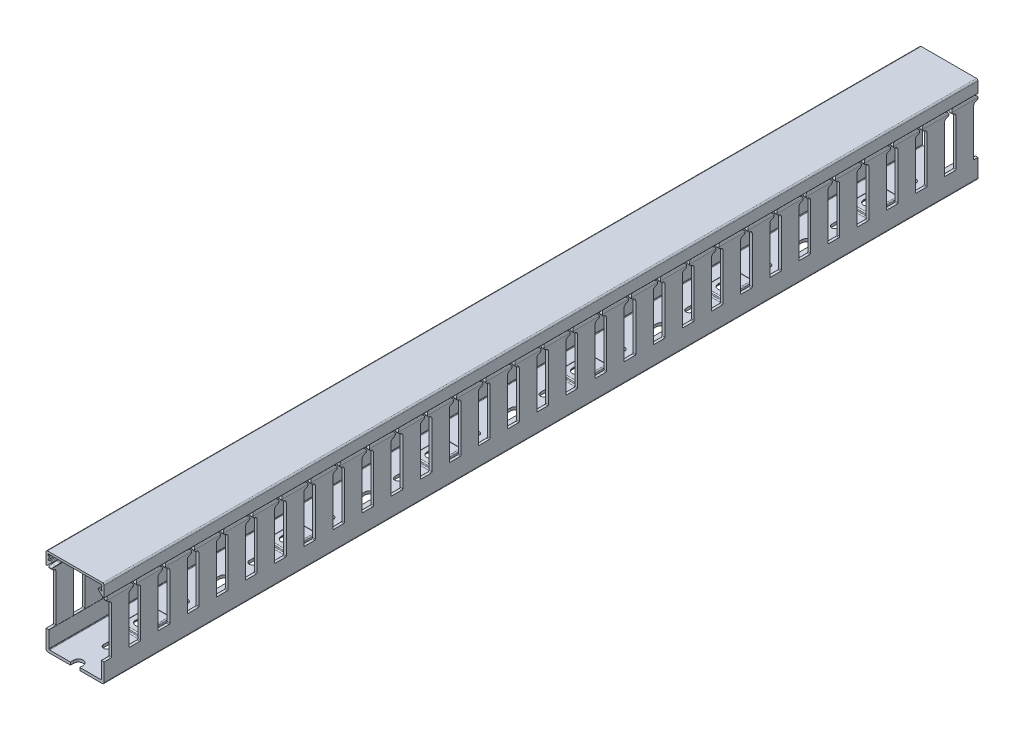
SolidWorks part; units mm, degrees
ref_plane "Front Plane" through (0, 0, 0) normal (0, 0, 1) x (1, 0, 0)
ref_plane "Top Plane" through (0, 0, 0) normal (0, 1, 0) x (1, 0, 0)
ref_plane "Right Plane" through (0, 0, 0) normal (1, 0, 0) x (0, 0, -1)
sketch "Sketch1" plane through (0, 0, 0) normal (0, 0, 1) x (1, 0, 0)
  line L0 (-18.2, -27.85) -> (-17.973, -27.983)
  line L1 (-20, -28.55) -> (-20, 19.1871)
  line L2 (-20, 21.7598) -> (-20, 29.05)
  line L3 (-18.5, 28.35) -> (-18.5, 27.55)
  line L4 (-18.5, 25.25) -> (-18.5, 25.058)
  line L5 (-19.6147, 20.1908) -> (-15.6798, 24.5609)
  line L6 (-17.8221, 24.7703) -> (-17.3671, 25.2097)
  line L7 (-15.9527, 24.4903) -> (-19.1527, 21.4001)
  line L8 (-18.1, 18.8416) -> (-18.1, -16.3923)
  line L9 (-18.1, -16.5077) -> (-18.1, -27.65)
  line L10 (-18, 25.55) -> (-18, 27.25)
  line L11 (-14.8603, 22.6316) -> (-17.9716, 19.1762)
  line L12 (-18.2, -16.45) -> (-18.1, -16.5077)
  line L13 (-13.3, 25.85) -> (-13.3, 24.6071)
  line L14 (-7, -28.15) -> (-7, -25.65)
  line L15 (-18.5, -30.05) -> (18.5, -30.05)
  line L16 (0, -30.05) -> (0, 30.05) construction
  line L18 (-17.6, -28.15) -> (17.6, -28.15)
  line L19 (-17.973, -27.983) -> (-17.973, -27.7208) construction
  line L20 (-18.082, -27.7829) -> (-17.973, -27.7208) construction
  line L21 (18.1, -16.5077) -> (18.1, -16.3923) construction
  line L23 (-7, -25.65) -> (7, -25.65)
  line L24 (-18.1, -16.5077) -> (-18.1, -16.3923) construction
  line L25 (-2.25, -30.05) -> (-2.25, -28.15)
  line L26 (2.25, -30.05) -> (2.25, -28.15)
  line L27 (7, -28.15) -> (7, -25.65)
  line L28 (17.973, -27.717) -> (18.082, -27.7829) construction
  line L29 (-18.1, -16.3923) -> (-18.2, -16.45)
  line L30 (18.1, -16.3923) -> (18.2, -16.45)
  line L31 (-18.082, -27.7829) -> (-18.2, -27.85)
  line L33 (18.4, 25.35) -> (18.2, 25.35)
  line L34 (-16.3, 25.35) -> (-17.0198, 25.35)
  line L35 (-18.4, 25.35) -> (-18.2, 25.35)
  line L36 (16.3, 25.35) -> (17.0198, 25.35)
  line L38 (-18.2, 27.45) -> (-18.4, 27.45)
  line L39 (18.2, 27.45) -> (18.4, 27.45)
  line L40 (16.0883, 27.65) -> (15.1, 27.65)
  line L41 (-16.0883, 27.65) -> (-15.1, 27.65)
  line L42 (-18.3, 28.55) -> (18.3, 28.55)
  line L44 (19, 30.05) -> (-19, 30.05)
  line L46 (-16.3812, 25.7055) -> (-17.6188, 25.3739)
  line L47 (16.3812, 25.7055) -> (17.6188, 25.3739)
  line L48 (13.3, 25.85) -> (13.3, 24.6071)
  line L49 (18, 25.55) -> (18, 27.25)
  line L50 (18.1, 18.8416) -> (18.1, -16.3923)
  line L51 (18.1, -16.5077) -> (18.1, -27.65)
  line L52 (18.5, 28.35) -> (18.5, 27.55)
  line L53 (18.5, 25.25) -> (18.5, 25.058)
  line L54 (18.2, -16.45) -> (18.1, -16.5077)
  line L55 (14.8603, 22.6316) -> (17.9716, 19.1762)
  line L56 (20, -28.55) -> (20, 19.1871)
  line L57 (20, 21.7598) -> (20, 29.05)
  line L58 (15.9527, 24.4903) -> (19.1527, 21.4001)
  line L59 (17.8221, 24.7703) -> (17.3671, 25.2097)
  line L60 (19.6147, 20.1908) -> (15.6798, 24.5609)
  line L61 (18.2, -27.85) -> (17.973, -27.983)
  line L62 (-2.25, -29.1) -> (2.25, -29.1) construction
  line L63 (-7, -26.9) -> (7, -26.9) construction
  line L64 (0, -29.1) -> (0, -26.9) construction
  line L68 (17.973, -27.983) -> (17.973, -27.717) construction
  line L69 (20, -4.6815) -> (18.1, -4.6815) construction
  line L70 (-20, -4.6815) -> (-18.1, -4.6815) construction
  line L71 (18.082, -27.7829) -> (18.2, -27.85)
  line L72 (16.4159, 20.9039) -> (17.8279, 22.1752) construction
  line L73 (18.2, -27.85) -> (17.973, -27.85) construction
  line L74 (20, 19.1871) -> (20, 19.7629) construction
  line L75 (20, 19.7629) -> (19.6147, 20.1908) construction
  line L76 (18.1, 18.8416) -> (18.1, 19.0335) construction
  line L77 (18.1, 19.0335) -> (17.9716, 19.1762) construction
  line L78 (20, 21.7598) -> (20, 20.5819) construction
  line L79 (20, 20.5819) -> (19.1527, 21.4001) construction
  line L80 (18.3, 28.55) -> (18.3, 30.05) construction
  line L81 (18.5, 28.35) -> (20, 28.35) construction
  line L82 (17.5946, 24.99) -> (16.5526, 23.911) construction
  line L83 (14.0985, 26.3171) -> (16.3812, 25.7055) construction
  line L84 (14.0985, 26.3171) -> (15.6798, 24.5609) construction
  line L85 (15.1, 24.6071) -> (15.1, 25.85) construction
  line L86 (15.1, 25.85) -> (16.0883, 25.85) construction
  line L87 (16.0883, 25.85) -> (16.0883, 24.6071) construction
  line L88 (16.0883, 24.6071) -> (15.1, 24.6071) construction
  arc A0 (-20, -28.55) -> (-18.5, -30.05) centre (-18.5, -28.55) ccw
  arc A1 (-18.1, -27.65) -> (-18.082, -27.7829) centre (-17.6, -27.65) ccw
  arc A2 (-17.973, -27.983) -> (-17.6, -28.15) centre (-17.6, -27.65) ccw
  arc A3 (-17.5208, 26.94) -> (-18.1276, 26.6686) centre (-15.7875, 22.25) ccw
  arc A4 (-14.8603, 22.6316) -> (-13.7623, 23.4026) centre (-15.9918, 25.41) ccw
  arc A5 (-16.0883, 27.65) -> (-17.5208, 26.94) centre (-16.0883, 25.85) ccw
  arc A6 (-13.3, 25.85) -> (-15.1, 27.65) centre (-15.1, 25.85) ccw
  arc A7 (-13.7623, 23.4026) -> (-13.3, 24.6071) centre (-15.1, 24.6071) ccw
  arc A8 (-19.6147, 20.1908) -> (-20, 19.1871) centre (-18.5, 19.1871) ccw
  arc A9 (-19, 30.05) -> (-20, 29.05) centre (-19, 29.05) ccw
  arc A10 (-15.6798, 24.5609) -> (-16.3812, 25.7055) centre (-16.2, 25.0293) ccw
  arc A11 (-18.1276, 26.6686) -> (-17.6188, 25.3739) centre (-17.8, 26.05) ccw
  arc A12 (-17.0198, 25.35) -> (-17.3671, 25.2097) centre (-17.0198, 24.85) ccw
  arc A13 (-15.9527, 24.4903) -> (-16.3, 25.35) centre (-16.3, 24.85) ccw
  arc A14 (-20, 21.7598) -> (-19.1527, 21.4001) centre (-19.5, 21.7598) ccw
  arc A15 (-17.9716, 19.1762) -> (-18.1, 18.8416) centre (-17.6, 18.8416) ccw
  arc A16 (-18.5, 25.058) -> (-17.8221, 24.7703) centre (-18.1, 25.058) ccw
  arc A17 (-18.3, 28.55) -> (-18.5, 28.35) centre (-18.3, 28.35) ccw
  arc A18 (-18, 27.25) -> (-18.2, 27.45) centre (-18.2, 27.25) ccw
  arc A19 (-18.2, 25.35) -> (-18, 25.55) centre (-18.2, 25.55) ccw
  arc A20 (-18.4, 25.35) -> (-18.5, 25.25) centre (-18.4, 25.25) ccw
  arc A21 (-18.5, 27.55) -> (-18.4, 27.45) centre (-18.4, 27.55) ccw
  arc A22 (18.5, -30.05) -> (20, -28.55) centre (18.5, -28.55) ccw
  arc A23 (17.6, -28.15) -> (17.973, -27.983) centre (17.6, -27.65) ccw
  arc A24 (18.082, -27.7829) -> (18.1, -27.65) centre (17.6, -27.65) ccw
  arc A25 (18.1276, 26.6686) -> (17.5208, 26.94) centre (15.7875, 22.25) ccw
  arc A26 (13.7623, 23.4026) -> (14.8603, 22.6316) centre (15.9918, 25.41) ccw
  arc A27 (13.3, 24.6071) -> (13.7623, 23.4026) centre (15.1, 24.6071) ccw
  arc A28 (15.1, 27.65) -> (13.3, 25.85) centre (15.1, 25.85) ccw
  arc A29 (17.5208, 26.94) -> (16.0883, 27.65) centre (16.0883, 25.85) ccw
  arc A30 (20, 19.1871) -> (19.6147, 20.1908) centre (18.5, 19.1871) ccw
  arc A31 (20, 29.05) -> (19, 30.05) centre (19, 29.05) ccw
  arc A32 (17.6188, 25.3739) -> (18.1276, 26.6686) centre (17.8, 26.05) ccw
  arc A33 (16.3812, 25.7055) -> (15.6798, 24.5609) centre (16.2, 25.0293) ccw
  arc A34 (17.3671, 25.2097) -> (17.0198, 25.35) centre (17.0198, 24.85) ccw
  arc A35 (16.3, 25.35) -> (15.9527, 24.4903) centre (16.3, 24.85) ccw
  arc A36 (19.1527, 21.4001) -> (20, 21.7598) centre (19.5, 21.7598) ccw
  arc A37 (18.1, 18.8416) -> (17.9716, 19.1762) centre (17.6, 18.8416) ccw
  arc A38 (17.8221, 24.7703) -> (18.5, 25.058) centre (18.1, 25.058) ccw
  arc A39 (18.5, 28.35) -> (18.3, 28.55) centre (18.3, 28.35) ccw
  arc A40 (18.2, 27.45) -> (18, 27.25) centre (18.2, 27.25) ccw
  arc A41 (18, 25.55) -> (18.2, 25.35) centre (18.2, 25.55) ccw
  arc A42 (18.5, 25.25) -> (18.4, 25.35) centre (18.4, 25.25) ccw
  arc A43 (18.4, 27.45) -> (18.5, 27.55) centre (18.4, 27.55) ccw
  point P188 (0, 28.55)
  dimension "D2" = 1.5
  dimension "D9" = 0.5
  dimension "D12" = 1
  dimension "D13" = 1.8
  dimension "D14" = 0.2
  dimension "D15" = 0.1
  dimension "D16" = 0.7
  dimension "D28" = 0.4
  dimension "D29" = 3
  dimension "D30" = 5
  dimension "D1" = 14
  dimension "Height" = 60.1
  dimension "Width" = 40
  dimension "D3" = 1.9
  dimension "D4" = 1.5
  dimension "D5" = 0.1155
  dimension "D6" = 46
  dimension "D7" = 138
  dimension "D10" = 2.5
  dimension "D11" = 4.5
  dimension "D18" = 0.3
  dimension "D19" = 0.266
  dimension "D20" = 60
  dimension "D21" = 8.6165
  dimension "D22" = 9.4681
  dimension "D23" = 0.5
  dimension "D24" = 1.1
  dimension "D25" = 2.1
  dimension "D26" = 0.9
  dimension "D27" = 4.8
  dimension "D31" = 0.9883
  dimension "D32" = 1.2429
  dimension "D33" = 33
  dimension "D34" = 5.0184
  dimension "D35" = 4.2208
  dimension "Slot Height" = 13.6
sketch "Sketch2" plane through (0, 0, 0) normal (0, 1, 0) x (1, 0, 0)
  line L1 (-20, 300) -> (20, 300)
  line L2 (-20, 300) -> (-20, -300)
  line L3 (-20, -300) -> (20, -300)
  line L4 (20, 300) -> (20, -300)
  line L5 (-20, 300) -> (20, -300) construction
  line L6 (-20, -300) -> (20, 300) construction
  line L9 (0, -305.25) -> (0, -297.75) construction
  line L10 (-3.25, -305.25) -> (-3.25, -297.75)
  line L11 (3.25, -305.25) -> (3.25, -297.75)
  line L15 (0, -294.5) -> (0, -297.75) construction
  line L16 (0, -305.25) -> (0, -308.5) construction
  line L17 (0, -278.25) -> (0, -274.75) construction
  line L18 (-2.25, -278.25) -> (-2.25, -274.75)
  line L19 (2.25, -278.25) -> (2.25, -274.75)
  line L23 (0, -278.25) -> (0, -280.5) construction
  line L24 (0, -255.25) -> (0, -247.75) construction
  line L26 (0, -274.75) -> (0, -272.5) construction
  line L30 (7, -262.2071) -> (-7, -262.2071)
  line L31 (7, -262.2071) -> (7, -240.7929)
  line L32 (7, -240.7929) -> (-7, -240.7929)
  line L33 (-7, -262.2071) -> (-7, -240.7929)
  line L34 (-3.25, -255.25) -> (-3.25, -247.75)
  line L35 (3.25, -255.25) -> (3.25, -247.75)
  line L36 (0, -205.25) -> (0, -197.75) construction
  line L37 (-3.25, -205.25) -> (-3.25, -197.75)
  line L38 (3.25, -205.25) -> (3.25, -197.75)
  line L45 (0, -228.25) -> (0, -224.75) construction
  line L46 (-2.25, -228.25) -> (-2.25, -224.75)
  line L47 (2.25, -228.25) -> (2.25, -224.75)
  arc A2 (-3.25, -305.25) -> (3.25, -305.25) centre (0, -305.25) ccw
  arc A3 (3.25, -297.75) -> (-3.25, -297.75) centre (0, -297.75) ccw
  arc A6 (-2.25, -278.25) -> (2.25, -278.25) centre (0, -278.25) ccw
  arc A7 (2.25, -274.75) -> (-2.25, -274.75) centre (0, -274.75) ccw
  arc A10 (-3.25, -255.25) -> (3.25, -255.25) centre (0, -255.25) ccw
  arc A11 (3.25, -247.75) -> (-3.25, -247.75) centre (0, -247.75) ccw
  arc A12 (-3.25, -205.25) -> (3.25, -205.25) centre (0, -205.25) ccw
  arc A13 (3.25, -197.75) -> (-3.25, -197.75) centre (0, -197.75) ccw
  arc A18 (-2.25, -228.25) -> (2.25, -228.25) centre (0, -228.25) ccw
  arc A19 (2.25, -224.75) -> (-2.25, -224.75) centre (0, -224.75) ccw
  point P0 (0, 0)
  point P14 (0, -301.5)
  point P33 (0, -276.5)
  point P67 (0, -251.5)
  point P74 (-7, -251.5)
  point P75 (0, -201.5)
  point P96 (0, -226.5)
  dimension "D1" = 5.5
  dimension "D2" = 14
  dimension "Length" = 600
  dimension "D3" = 6.5
  dimension "D4" = 8
  dimension "D5" = 23.5
  dimension "D6" = 21.4142
  dimension "D7" = 25
  dimension "Slot Spacing 2" = 100
  dimension "Slot Spacing 1" = 50
sketch "Sketch3" plane through (0, 0, 0) normal (0, 0, 1) x (1, 0, 0)
  line L0 (15.9527, 24.4903) -> (19.1527, 21.4001) construction
  line L1 (16.3, 25.35) -> (17.0198, 25.35) construction
  line L2 (17.8221, 24.7703) -> (17.3671, 25.2097) construction
  line L3 (18.5, 25.25) -> (18.5, 25.058) construction
  line L4 (18.4, 25.35) -> (18.2, 25.35) construction
  line L5 (18, 25.55) -> (18, 27.25) construction
  line L6 (18.2, 27.45) -> (18.4, 27.45) construction
  line L7 (18.5, 28.35) -> (18.5, 27.55) construction
  line L8 (20, 21.7598) -> (20, 29.05) construction
  line L9 (19, 30.05) -> (-19, 30.05) construction
  line L10 (-18.3, 28.55) -> (18.3, 28.55) construction
  line L11 (-18.5, 28.35) -> (-18.5, 27.55) construction
  line L12 (-18.2, 27.45) -> (-18.4, 27.45) construction
  line L13 (-18, 25.55) -> (-18, 27.25) construction
  line L14 (-18.4, 25.35) -> (-18.2, 25.35) construction
  line L15 (-18.5, 25.25) -> (-18.5, 25.058) construction
  line L16 (-17.8221, 24.7703) -> (-17.3671, 25.2097) construction
  line L17 (-16.3, 25.35) -> (-17.0198, 25.35) construction
  line L18 (-15.9527, 24.4903) -> (-19.1527, 21.4001) construction
  line L19 (-20, 21.7598) -> (-20, 29.05) construction
  line L20 (15.9527, 24.4903) -> (19.1527, 21.4001)
  line L21 (16.3, 25.35) -> (17.0198, 25.35)
  line L22 (17.8221, 24.7703) -> (17.3671, 25.2097)
  line L23 (18.5, 25.25) -> (18.5, 25.058)
  line L24 (18.4, 25.35) -> (18.2, 25.35)
  line L25 (18, 25.55) -> (18, 27.25)
  line L26 (18.2, 27.45) -> (18.4, 27.45)
  line L27 (18.5, 28.35) -> (18.5, 27.55)
  line L28 (20, 21.7598) -> (20, 29.05)
  line L29 (19, 30.05) -> (-19, 30.05)
  line L30 (-18.3, 28.55) -> (18.3, 28.55)
  line L31 (-18.5, 28.35) -> (-18.5, 27.55)
  line L32 (-18.2, 27.45) -> (-18.4, 27.45)
  line L33 (-18, 25.55) -> (-18, 27.25)
  line L34 (-18.4, 25.35) -> (-18.2, 25.35)
  line L35 (-18.5, 25.25) -> (-18.5, 25.058)
  line L36 (-17.8221, 24.7703) -> (-17.3671, 25.2097)
  line L37 (-16.3, 25.35) -> (-17.0198, 25.35)
  line L38 (-15.9527, 24.4903) -> (-19.1527, 21.4001)
  line L39 (-20, 21.7598) -> (-20, 29.05)
  arc A0 (19.1527, 21.4001) -> (20, 21.7598) centre (19.5, 21.7598) ccw construction
  arc A1 (16.3, 25.35) -> (15.9527, 24.4903) centre (16.3, 24.85) ccw construction
  arc A2 (17.3671, 25.2097) -> (17.0198, 25.35) centre (17.0198, 24.85) ccw construction
  arc A3 (17.8221, 24.7703) -> (18.5, 25.058) centre (18.1, 25.058) ccw construction
  arc A4 (18.5, 25.25) -> (18.4, 25.35) centre (18.4, 25.25) ccw construction
  arc A5 (18, 25.55) -> (18.2, 25.35) centre (18.2, 25.55) ccw construction
  arc A6 (18.2, 27.45) -> (18, 27.25) centre (18.2, 27.25) ccw construction
  arc A7 (18.4, 27.45) -> (18.5, 27.55) centre (18.4, 27.55) ccw construction
  arc A8 (18.5, 28.35) -> (18.3, 28.55) centre (18.3, 28.35) ccw construction
  arc A9 (20, 29.05) -> (19, 30.05) centre (19, 29.05) ccw construction
  arc A10 (-18.3, 28.55) -> (-18.5, 28.35) centre (-18.3, 28.35) ccw construction
  arc A11 (-18.5, 27.55) -> (-18.4, 27.45) centre (-18.4, 27.55) ccw construction
  arc A12 (-18, 27.25) -> (-18.2, 27.45) centre (-18.2, 27.25) ccw construction
  arc A13 (-18.2, 25.35) -> (-18, 25.55) centre (-18.2, 25.55) ccw construction
  arc A14 (-18.4, 25.35) -> (-18.5, 25.25) centre (-18.4, 25.25) ccw construction
  arc A15 (-18.5, 25.058) -> (-17.8221, 24.7703) centre (-18.1, 25.058) ccw construction
  arc A16 (-17.0198, 25.35) -> (-17.3671, 25.2097) centre (-17.0198, 24.85) ccw construction
  arc A17 (-15.9527, 24.4903) -> (-16.3, 25.35) centre (-16.3, 24.85) ccw construction
  arc A18 (-20, 21.7598) -> (-19.1527, 21.4001) centre (-19.5, 21.7598) ccw construction
  arc A19 (-19, 30.05) -> (-20, 29.05) centre (-19, 29.05) ccw construction
  arc A20 (19.1527, 21.4001) -> (20, 21.7598) centre (19.5, 21.7598) ccw
  arc A21 (16.3, 25.35) -> (15.9527, 24.4903) centre (16.3, 24.85) ccw
  arc A22 (17.3671, 25.2097) -> (17.0198, 25.35) centre (17.0198, 24.85) ccw
  arc A23 (17.8221, 24.7703) -> (18.5, 25.058) centre (18.1, 25.058) ccw
  arc A24 (18.5, 25.25) -> (18.4, 25.35) centre (18.4, 25.25) ccw
  arc A25 (18, 25.55) -> (18.2, 25.35) centre (18.2, 25.55) ccw
  arc A26 (18.2, 27.45) -> (18, 27.25) centre (18.2, 27.25) ccw
  arc A27 (18.4, 27.45) -> (18.5, 27.55) centre (18.4, 27.55) ccw
  arc A28 (18.5, 28.35) -> (18.3, 28.55) centre (18.3, 28.35) ccw
  arc A29 (20, 29.05) -> (19, 30.05) centre (19, 29.05) ccw
  arc A30 (-18.3, 28.55) -> (-18.5, 28.35) centre (-18.3, 28.35) ccw
  arc A31 (-18.5, 27.55) -> (-18.4, 27.45) centre (-18.4, 27.55) ccw
  arc A32 (-18, 27.25) -> (-18.2, 27.45) centre (-18.2, 27.25) ccw
  arc A33 (-18.2, 25.35) -> (-18, 25.55) centre (-18.2, 25.55) ccw
  arc A34 (-18.4, 25.35) -> (-18.5, 25.25) centre (-18.4, 25.25) ccw
  arc A35 (-18.5, 25.058) -> (-17.8221, 24.7703) centre (-18.1, 25.058) ccw
  arc A36 (-17.0198, 25.35) -> (-17.3671, 25.2097) centre (-17.0198, 24.85) ccw
  arc A37 (-15.9527, 24.4903) -> (-16.3, 25.35) centre (-16.3, 24.85) ccw
  arc A38 (-20, 21.7598) -> (-19.1527, 21.4001) centre (-19.5, 21.7598) ccw
  arc A39 (-19, 30.05) -> (-20, 29.05) centre (-19, 29.05) ccw
extrude "Boss-Extrude1" add sketch "Sketch3" along normal up to vertex (300 mm away) from vertex separate body up to point (20, 0, 300) starting at point (20, 0, -300)
sketch "Sketch4" plane through (0, 0, 0) normal (0, 0, 1) x (1, 0, 0)
  line L0 (18.2, -27.85) -> (17.973, -27.983) construction
  line L1 (18.082, -27.7829) -> (18.2, -27.85) construction
  line L2 (18.1, -16.5077) -> (18.1, -27.65) construction
  line L3 (18.2, -16.45) -> (18.1, -16.5077) construction
  line L4 (18.1, -16.3923) -> (18.2, -16.45) construction
  line L5 (20, -28.55) -> (20, 19.1871) construction
  line L6 (18.1, 18.8416) -> (18.1, -16.3923) construction
  line L7 (19.6147, 20.1908) -> (15.6798, 24.5609) construction
  line L8 (16.3812, 25.7055) -> (17.6188, 25.3739) construction
  line L9 (14.8603, 22.6316) -> (17.9716, 19.1762) construction
  line L10 (13.3, 25.85) -> (13.3, 24.6071) construction
  line L11 (16.0883, 27.65) -> (15.1, 27.65) construction
  line L12 (-16.3812, 25.7055) -> (-17.6188, 25.3739) construction
  line L13 (-16.0883, 27.65) -> (-15.1, 27.65) construction
  line L14 (-13.3, 25.85) -> (-13.3, 24.6071) construction
  line L15 (-19.6147, 20.1908) -> (-15.6798, 24.5609) construction
  line L16 (-14.8603, 22.6316) -> (-17.9716, 19.1762) construction
  line L17 (-18.1, 18.8416) -> (-18.1, -16.3923) construction
  line L18 (-18.1, -16.3923) -> (-18.2, -16.45) construction
  line L19 (-18.2, -16.45) -> (-18.1, -16.5077) construction
  line L20 (-18.1, -16.5077) -> (-18.1, -27.65) construction
  line L21 (-18.082, -27.7829) -> (-18.2, -27.85) construction
  line L22 (-18.2, -27.85) -> (-17.973, -27.983) construction
  line L23 (-17.6, -28.15) -> (17.6, -28.15) construction
  line L24 (-18.5, -30.05) -> (18.5, -30.05) construction
  line L25 (-20, -28.55) -> (-20, 19.1871) construction
  line L26 (18.2, -27.85) -> (17.973, -27.983)
  line L27 (18.082, -27.7829) -> (18.2, -27.85)
  line L28 (18.1, -16.5077) -> (18.1, -27.65)
  line L29 (18.2, -16.45) -> (18.1, -16.5077)
  line L30 (18.1, -16.3923) -> (18.2, -16.45)
  line L31 (20, -28.55) -> (20, 19.1871)
  line L32 (18.1, 18.8416) -> (18.1, -16.3923)
  line L33 (19.6147, 20.1908) -> (15.6798, 24.5609)
  line L34 (16.3812, 25.7055) -> (17.6188, 25.3739)
  line L35 (14.8603, 22.6316) -> (17.9716, 19.1762)
  line L36 (13.3, 25.85) -> (13.3, 24.6071)
  line L37 (16.0883, 27.65) -> (15.1, 27.65)
  line L38 (-16.3812, 25.7055) -> (-17.6188, 25.3739)
  line L39 (-16.0883, 27.65) -> (-15.1, 27.65)
  line L40 (-13.3, 25.85) -> (-13.3, 24.6071)
  line L41 (-19.6147, 20.1908) -> (-15.6798, 24.5609)
  line L42 (-14.8603, 22.6316) -> (-17.9716, 19.1762)
  line L43 (-18.1, 18.8416) -> (-18.1, -16.3923)
  line L44 (-18.1, -16.3923) -> (-18.2, -16.45)
  line L45 (-18.2, -16.45) -> (-18.1, -16.5077)
  line L46 (-18.1, -16.5077) -> (-18.1, -27.65)
  line L47 (-18.082, -27.7829) -> (-18.2, -27.85)
  line L48 (-18.2, -27.85) -> (-17.973, -27.983)
  line L49 (-17.6, -28.15) -> (17.6, -28.15)
  line L50 (-18.5, -30.05) -> (18.5, -30.05)
  line L51 (-20, -28.55) -> (-20, 19.1871)
  arc A0 (18.5, -30.05) -> (20, -28.55) centre (18.5, -28.55) ccw construction
  arc A1 (17.6, -28.15) -> (17.973, -27.983) centre (17.6, -27.65) ccw construction
  arc A2 (18.082, -27.7829) -> (18.1, -27.65) centre (17.6, -27.65) ccw construction
  arc A3 (18.1, 18.8416) -> (17.9716, 19.1762) centre (17.6, 18.8416) ccw construction
  arc A4 (20, 19.1871) -> (19.6147, 20.1908) centre (18.5, 19.1871) ccw construction
  arc A5 (16.3812, 25.7055) -> (15.6798, 24.5609) centre (16.2, 25.0293) ccw construction
  arc A6 (13.7623, 23.4026) -> (14.8603, 22.6316) centre (15.9918, 25.41) ccw construction
  arc A7 (13.3, 24.6071) -> (13.7623, 23.4026) centre (15.1, 24.6071) ccw construction
  arc A8 (15.1, 27.65) -> (13.3, 25.85) centre (15.1, 25.85) ccw construction
  arc A9 (17.5208, 26.94) -> (16.0883, 27.65) centre (16.0883, 25.85) ccw construction
  arc A10 (18.1276, 26.6686) -> (17.5208, 26.94) centre (15.7875, 22.25) ccw construction
  arc A11 (17.6188, 25.3739) -> (18.1276, 26.6686) centre (17.8, 26.05) ccw construction
  arc A12 (-15.6798, 24.5609) -> (-16.3812, 25.7055) centre (-16.2, 25.0293) ccw construction
  arc A13 (-18.1276, 26.6686) -> (-17.6188, 25.3739) centre (-17.8, 26.05) ccw construction
  arc A14 (-17.5208, 26.94) -> (-18.1276, 26.6686) centre (-15.7875, 22.25) ccw construction
  arc A15 (-16.0883, 27.65) -> (-17.5208, 26.94) centre (-16.0883, 25.85) ccw construction
  arc A16 (-13.3, 25.85) -> (-15.1, 27.65) centre (-15.1, 25.85) ccw construction
  arc A17 (-13.7623, 23.4026) -> (-13.3, 24.6071) centre (-15.1, 24.6071) ccw construction
  arc A18 (-14.8603, 22.6316) -> (-13.7623, 23.4026) centre (-15.9918, 25.41) ccw construction
  arc A19 (-17.9716, 19.1762) -> (-18.1, 18.8416) centre (-17.6, 18.8416) ccw construction
  arc A20 (-19.6147, 20.1908) -> (-20, 19.1871) centre (-18.5, 19.1871) ccw construction
  arc A21 (-18.1, -27.65) -> (-18.082, -27.7829) centre (-17.6, -27.65) ccw construction
  arc A22 (-17.973, -27.983) -> (-17.6, -28.15) centre (-17.6, -27.65) ccw construction
  arc A23 (-20, -28.55) -> (-18.5, -30.05) centre (-18.5, -28.55) ccw construction
  arc A24 (18.5, -30.05) -> (20, -28.55) centre (18.5, -28.55) ccw
  arc A25 (17.6, -28.15) -> (17.973, -27.983) centre (17.6, -27.65) ccw
  arc A26 (18.082, -27.7829) -> (18.1, -27.65) centre (17.6, -27.65) ccw
  arc A27 (18.1, 18.8416) -> (17.9716, 19.1762) centre (17.6, 18.8416) ccw
  arc A28 (20, 19.1871) -> (19.6147, 20.1908) centre (18.5, 19.1871) ccw
  arc A29 (16.3812, 25.7055) -> (15.6798, 24.5609) centre (16.2, 25.0293) ccw
  arc A30 (13.7623, 23.4026) -> (14.8603, 22.6316) centre (15.9918, 25.41) ccw
  arc A31 (13.3, 24.6071) -> (13.7623, 23.4026) centre (15.1, 24.6071) ccw
  arc A32 (15.1, 27.65) -> (13.3, 25.85) centre (15.1, 25.85) ccw
  arc A33 (17.5208, 26.94) -> (16.0883, 27.65) centre (16.0883, 25.85) ccw
  arc A34 (18.1276, 26.6686) -> (17.5208, 26.94) centre (15.7875, 22.25) ccw
  arc A35 (17.6188, 25.3739) -> (18.1276, 26.6686) centre (17.8, 26.05) ccw
  arc A36 (-15.6798, 24.5609) -> (-16.3812, 25.7055) centre (-16.2, 25.0293) ccw
  arc A37 (-18.1276, 26.6686) -> (-17.6188, 25.3739) centre (-17.8, 26.05) ccw
  arc A38 (-17.5208, 26.94) -> (-18.1276, 26.6686) centre (-15.7875, 22.25) ccw
  arc A39 (-16.0883, 27.65) -> (-17.5208, 26.94) centre (-16.0883, 25.85) ccw
  arc A40 (-13.3, 25.85) -> (-15.1, 27.65) centre (-15.1, 25.85) ccw
  arc A41 (-13.7623, 23.4026) -> (-13.3, 24.6071) centre (-15.1, 24.6071) ccw
  arc A42 (-14.8603, 22.6316) -> (-13.7623, 23.4026) centre (-15.9918, 25.41) ccw
  arc A43 (-17.9716, 19.1762) -> (-18.1, 18.8416) centre (-17.6, 18.8416) ccw
  arc A44 (-19.6147, 20.1908) -> (-20, 19.1871) centre (-18.5, 19.1871) ccw
  arc A45 (-18.1, -27.65) -> (-18.082, -27.7829) centre (-17.6, -27.65) ccw
  arc A46 (-17.973, -27.983) -> (-17.6, -28.15) centre (-17.6, -27.65) ccw
  arc A47 (-20, -28.55) -> (-18.5, -30.05) centre (-18.5, -28.55) ccw
extrude "Boss-Extrude2" add sketch "Sketch4" along normal up to vertex (300 mm away) from vertex separate body up to point (20, 0, 300) starting at point (20, 0, -300)
sketch "Sketch5" plane through (0, 0, 0) normal (0, 1, 0) x (1, 0, 0)
  line L4 (7, -240.7929) -> (-7, -240.7929) construction
  line L5 (7, -262.2071) -> (7, -240.7929) construction
  line L6 (7, -262.2071) -> (-7, -262.2071) construction
  line L7 (-7, -262.2071) -> (-7, -240.7929) construction
  line L12 (7, -240.7929) -> (-7, -240.7929)
  line L13 (7, -262.2071) -> (7, -240.7929)
  line L14 (7, -262.2071) -> (-7, -262.2071)
  line L15 (-7, -262.2071) -> (-7, -240.7929)
extrude "Boss-Extrude3" add sketch "Sketch5" along normal up to vertex (-25.65 mm away) from vertex up to point (7, -25.65, 0) starting at point (0, -30.05, 0)
sketch "Sketch6" plane through (0, 0, 0) normal (0, 1, 0) x (1, 0, 0)
  line L4 (-7, -262.2071) -> (-7, -240.7929) construction
  line L5 (7, -240.7929) -> (-7, -240.7929) construction
  line L6 (7, -262.2071) -> (7, -240.7929) construction
  line L7 (7, -262.2071) -> (-7, -262.2071) construction
  line L12 (-7, -262.2071) -> (-7, -240.7929) construction
  line L13 (7, -240.7929) -> (-7, -240.7929) construction
  line L14 (7, -262.2071) -> (7, -240.7929) construction
  line L15 (7, -262.2071) -> (-7, -262.2071) construction
  line L16 (6.268, -261.4751) -> (6.268, -241.5249)
  line L17 (6.268, -241.5249) -> (-6.268, -241.5249)
  line L18 (-6.268, -261.4751) -> (-6.268, -241.5249)
  line L19 (6.268, -261.4751) -> (-6.268, -261.4751)
  dimension "D1" = 0.732
extrude "Cut-Extrude1" cut sketch "Sketch6" along normal blind 3.6678 from vertex starting at point (0, -30.05, 0)
fillet "Fillet1" radius 0.732 24 edges at (0, -28.15, 240.7929) (7, -26.9, 240.7929) (7, -28.15, 251.5) (-7, -28.15, 251.5) (-7, -26.9, 240.7929) (7, -26.9, 262.2071) (0, -28.15, 262.2071) (-7, -26.9, 262.2071) (0, -25.65, 262.2071) (-7, -25.65, 251.5) (0, -25.65, 240.7929) (7, -25.65, 251.5) (0, -26.3822, 241.5249) (0, -30.05, 241.5249) (-6.268, -26.3822, 251.5) (-6.268, -30.05, 251.5) (0, -26.3822, 261.4751) (0, -30.05, 261.4751) (6.268, -26.3822, 251.5) (6.268, -30.05, 251.5) (-6.268, -28.2161, 241.5249) (-6.268, -28.2161, 261.4751) (6.268, -28.2161, 241.5249) (6.268, -28.2161, 261.4751)
pattern_linear "LPattern1" count 6 spacing 100 along (0, 0, -1) of "Boss-Extrude3", "Cut-Extrude1", "Fillet1"
sketch "Sketch7" plane through (0, 0, 0) normal (0, 1, 0) x (1, 0, 0)
  line L4 (-2.25, -228.25) -> (-2.25, -224.75) construction
  line L6 (-3.25, -255.25) -> (-3.25, -247.75) construction
  line L7 (-2.25, -278.25) -> (-2.25, -274.75) construction
  line L10 (-3.25, -305.25) -> (-3.25, -297.75) construction
  line L16 (-2.25, -228.25) -> (-2.25, -224.75)
  line L18 (-3.25, -255.25) -> (-3.25, -247.75)
  line L19 (-2.25, -278.25) -> (-2.25, -274.75)
  line L22 (-3.25, -305.25) -> (-3.25, -297.75)
  line L28 (2.25, -228.25) -> (2.25, -224.75) construction
  line L30 (3.25, -255.25) -> (3.25, -247.75) construction
  line L31 (2.25, -278.25) -> (2.25, -274.75) construction
  line L34 (3.25, -305.25) -> (3.25, -297.75) construction
  line L40 (2.25, -228.25) -> (2.25, -224.75)
  line L42 (3.25, -255.25) -> (3.25, -247.75)
  line L43 (2.25, -278.25) -> (2.25, -274.75)
  line L46 (3.25, -305.25) -> (3.25, -297.75)
  line L54 (0, -276.5) -> (0, -226.5) construction
  arc A8 (-2.25, -228.25) -> (2.25, -228.25) centre (0, -228.25) ccw construction
  arc A9 (2.25, -224.75) -> (-2.25, -224.75) centre (0, -224.75) ccw construction
  arc A12 (-3.25, -255.25) -> (3.25, -255.25) centre (0, -255.25) ccw construction
  arc A13 (3.25, -247.75) -> (-3.25, -247.75) centre (0, -247.75) ccw construction
  arc A14 (-2.25, -278.25) -> (2.25, -278.25) centre (0, -278.25) ccw construction
  arc A15 (2.25, -274.75) -> (-2.25, -274.75) centre (0, -274.75) ccw construction
  arc A20 (-3.25, -305.25) -> (3.25, -305.25) centre (0, -305.25) ccw construction
  arc A21 (3.25, -297.75) -> (-3.25, -297.75) centre (0, -297.75) ccw construction
  arc A32 (-2.25, -228.25) -> (2.25, -228.25) centre (0, -228.25) ccw
  arc A33 (2.25, -224.75) -> (-2.25, -224.75) centre (0, -224.75) ccw
  arc A36 (-3.25, -255.25) -> (3.25, -255.25) centre (0, -255.25) ccw
  arc A37 (3.25, -247.75) -> (-3.25, -247.75) centre (0, -247.75) ccw
  arc A38 (-2.25, -278.25) -> (2.25, -278.25) centre (0, -278.25) ccw
  arc A39 (2.25, -274.75) -> (-2.25, -274.75) centre (0, -274.75) ccw
  arc A44 (-3.25, -305.25) -> (3.25, -305.25) centre (0, -305.25) ccw
  arc A45 (3.25, -297.75) -> (-3.25, -297.75) centre (0, -297.75) ccw
extrude "Cut-Extrude2" cut sketch "Sketch7" against normal through all both and the other way through all
pattern_linear "LPattern2" count 7 spacing 100 along (0, 0, -1) of "Cut-Extrude2"
sketch "Sketch8" plane through (0, 0, 0) normal (1, 0, 0) x (0, 0, -1)
  line L0 (-303, 15.6859) -> (-303, -15.95)
  line L1 (-295, -15.95) -> (-295, 15.6859)
  line L2 (-301, 15.6859) -> (-297, 15.6859) construction
  line L3 (-302.5, -16.45) -> (-295.5, -16.45)
  line L4 (-297, 15.6859) -> (-297, 22.6141) construction
  line L5 (-297, 22.6141) -> (-301, 22.6141) construction
  line L6 (-303, 51.2859) -> (-303, 22.6141)
  line L7 (-295, 22.6141) -> (-295, 51.2859)
  line L9 (-301.5, 19.15) -> (-296.5, 19.15) construction
  line L11 (-301, 22.6141) -> (-301, 15.6859) construction
  line L13 (-303, 36.95) -> (-295, 36.95) construction
  line L15 (-303, 58.2141) -> (-303, 90.35)
  line L16 (-303, 90.35) -> (-295, 90.35)
  line L17 (-295, 90.35) -> (-295, 58.2141)
  line L18 (-296.5, 19.15) -> (-296.5, 54.75) construction
  line L19 (-296.5, 54.75) -> (-296.5, 90.35) construction
  line L20 (-296.5, 19.15) -> (-296.5, -16.45) construction
  arc A2 (-295.5, -16.45) -> (-295, -15.95) centre (-295.5, -15.95) ccw
  arc A3 (-303, -15.95) -> (-302.5, -16.45) centre (-302.5, -15.95) ccw
  arc A4 (-301.2857, 17.6654) -> (-303, 15.6859) centre (-301, 15.6859) ccw
  arc A5 (-303, 22.6141) -> (-301.2857, 20.6346) centre (-301, 22.6141) ccw
  arc A6 (-301.2857, 17.6654) -> (-301.2857, 20.6346) centre (-301.5, 19.15) ccw
  arc A9 (-296.7143, 17.6654) -> (-295, 15.6859) centre (-297, 15.6859) cw
  arc A11 (-296.7143, 17.6654) -> (-296.7143, 20.6346) centre (-296.5, 19.15) cw
  arc A14 (-295, 22.6141) -> (-296.7143, 20.6346) centre (-297, 22.6141) cw
  arc A15 (-295, 51.2859) -> (-296.7143, 53.2654) centre (-297, 51.2859) ccw
  arc A16 (-296.7143, 56.2346) -> (-296.7143, 53.2654) centre (-296.5, 54.75) ccw
  arc A17 (-296.7143, 56.2346) -> (-295, 58.2141) centre (-297, 58.2141) ccw
  arc A18 (-301.2857, 56.2346) -> (-303, 58.2141) centre (-301, 58.2141) cw
  arc A19 (-301.2857, 56.2346) -> (-301.2857, 53.2654) centre (-301.5, 54.75) cw
  arc A20 (-303, 51.2859) -> (-301.2857, 53.2654) centre (-301, 51.2859) cw
  point P36 (-219, -16.45)
  point P38 (-299, -16.45)
  point P40 (-239, -16.45)
  point P42 (-298, 19.15)
  point P45 (-300, 19.15)
  dimension "D3" = 0.5
  dimension "D4" = 2
  dimension "D5" = 1.5
  dimension "D1" = 8
  dimension "D2" = 6.9282
  dimension "D6" = 80
  dimension "D7" = 2
  dimension "D8" = 20
  dimension "Wire Slot Height Space" = 35.6
extrude "Cut-Extrude3" cut sketch "Sketch8" against normal through all both and the other way through all
pattern_linear "LPattern4" count 32 spacing 20 along (0, 0, -1) of "Cut-Extrude3"
equation "\"D3@LPattern1\"=\"Slot Spacing 2@Sketch2\""
equation "\"D1@LPattern1\"=Round(\"Length@Sketch2\"/\"Slot Spacing 2@Sketch2\")"
equation "\"D3@LPattern2\"=\"Slot Spacing 2@Sketch2\""
equation "\"D1@LPattern2\"=Round(\"Length@Sketch2\"/\"Slot Spacing 2@Sketch2\")+1"
equation "\"D1@LPattern4\"=Round(\"Length@Sketch2\"/\"D3@LPattern4\")+2"
